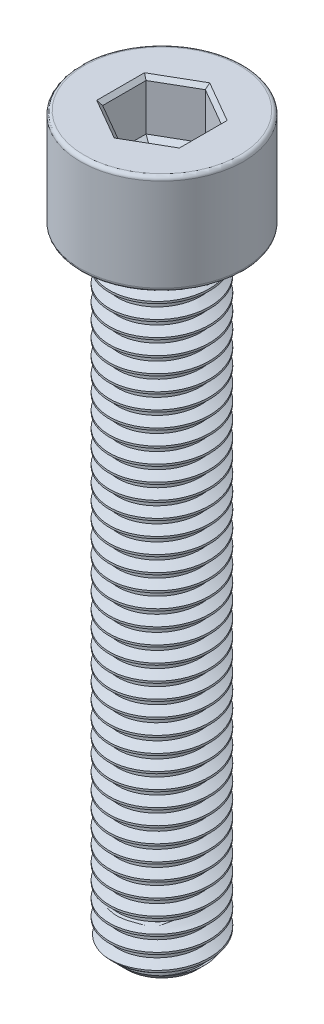
SolidWorks part; units mm, degrees
material "AISI Type A2 Tool Steel"
ref_plane "Front Plane" through (0, 0, 0) normal (0, 0, 1) x (1, 0, 0)
ref_plane "Top Plane" through (0, 0, 0) normal (0, 1, 0) x (1, 0, 0)
ref_plane "Right Plane" through (0, 0, 0) normal (1, 0, 0) x (0, 0, -1)
sketch "Sketch1" plane through (0, 0, 0) normal (0, 1, 0) x (1, 0, 0)
  circle A0 centre (0, 0) radius 4
  dimension "D1" = 8
extrude "Boss-Extrude1" add sketch "Sketch1" along normal blind 50
thread "Thread1" pitch 1.25 profile "Thread Profile1" start angle 0, offset 2, length 0, pitch 1.25, diameter 8
ref_plane "Plane1" through (-4, 52, 0) normal (0, 0, 1) x (-1, 0, 0)
sketch "Thread Profile1" plane through (-4, 52, 0) normal (0, 0, 1) x (-1, 0, 0)
  line L0 (0, 0) -> (0, 1.25) construction
  line L11 (0, 0) -> (0, 1.0937)
  line L12 (0, 1.0937) -> (-0.6766, 0.7031)
  line L13 (-0.6766, 0.7031) -> (-0.6766, 0.3906)
  line L15 (-0.6766, 0.3906) -> (0, 0)
  line L17 (-0.6766, 0.5469) -> (0, 0.5469) construction
  point P2 (0, 0)
  dimension "Pitch" = 1.25
  dimension "Profile_Angle" = 60
  dimension "Profile_Land" = 0.3125
  dimension "Profile_Height" = 0.6766
sketch "Sketch2" plane through (0, 50, 0) normal (0, 1, 0) x (1, 0, 0)
  circle A0 centre (0, 0) radius 6.5
  dimension "D1" = 13
extrude "Boss-Extrude2" add sketch "Sketch2" along normal blind 8
sketch "Sketch5" plane through (0, 0, 0) normal (0, 0, 1) x (1, 0, 0)
  line L0 (0, 0) -> (0, 0.9986) construction
  line L1 (0, 0) -> (4.01, 0) construction
  line L2 (4.01, 0) -> (4.01, 1.2)
  line L3 (4.01, 1.2) -> (2.81, 0)
  line L4 (2.81, 0) -> (4.01, 0)
  dimension "D1" = 1.2
  dimension "D2" = 45
  dimension "D3" = 4.01
revolve "Cut-Revolve1" cut sketch "Sketch5" angle 360 about L0
fillet "Fillet1" radius 0.3 2 edges at (0, 58, 6.5) (0, 50, 6.5)
sketch "Sketch6" plane through (0, 58, 0) normal (0, 1, 0) x (1, 0, 0)
  line L1 (0, 3.4641) -> (-3, 1.7321)
  line L2 (-3, 1.7321) -> (-3, -1.7321)
  line L3 (-3, -1.7321) -> (0, -3.4641)
  line L4 (0, -3.4641) -> (3, -1.7321)
  line L5 (3, -1.7321) -> (3, 1.7321)
  line L6 (3, 1.7321) -> (0, 3.4641)
  circle A0 centre (0, 0) radius 3 construction
  dimension "D1" = 6
extrude "Cut-Extrude1" cut sketch "Sketch6" against normal blind 4
chamfer "Chamfer1" distance 0.3 angle 45 6 edges at (-3, 58, 0) (-1.5, 58, 2.5981) (1.5, 58, 2.5981) (3, 58, 0) (1.5, 58, -2.5981) (-1.5, 58, -2.5981)
sketch "Sketch7" plane through (0, 54, 0) normal (0, 1, 0) x (1, 0, 0)
  line L1 (0, 3.4641) -> (-3, 1.7321)
  line L2 (-3, 1.7321) -> (-3, -1.7321)
  line L3 (-3, -1.7321) -> (0, -3.4641)
  line L4 (0, -3.4641) -> (3, -1.7321)
  line L5 (3, -1.7321) -> (3, 1.7321)
  line L6 (3, 1.7321) -> (0, 3.4641)
  circle A0 centre (0, 0) radius 3 construction
extrude "Cut-Extrude2" cut sketch "Sketch7" against normal blind 0.4 draft 60
